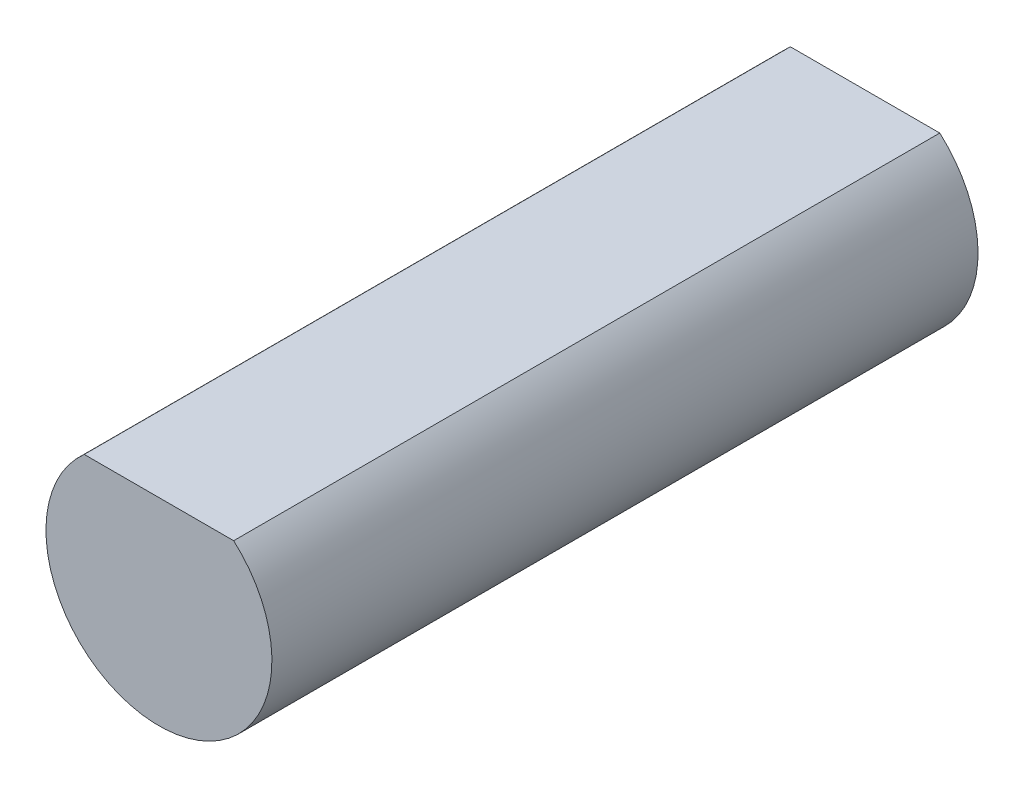
SolidWorks part; units mm, degrees
ref_plane "Front Plane" through (0, 0, 0) normal (0, 0, 1) x (1, 0, 0)
ref_plane "Top Plane" through (0, 0, 0) normal (0, 1, 0) x (1, 0, 0)
ref_plane "Right Plane" through (0, 0, 0) normal (1, 0, 0) x (0, 0, -1)
sketch "Sketch2" plane through (0, 0, 0) normal (0, 0, 1) x (1, 0, 0)
  circle A0 centre (0, 0) radius 4
  dimension "D1" = 8
extrude "Boss-Extrude1" add sketch "Sketch2" along normal blind 25
sketch "Sketch3" plane through (0, 0, 25) normal (0, 0, 1) x (1, 0, 0)
  line L0 (-2.6458, 3) -> (2.6458, 3)
  line L1 (0, 0) -> (0, 3) construction
  circle A0 centre (0, 0) radius 4 construction
  arc A1 (2.6458, 3) -> (-2.6458, 3) centre (0, 0) ccw
  dimension "D1" = 3
extrude "Cut-Extrude1" cut sketch "Sketch3" against normal up to next and the other way through all
